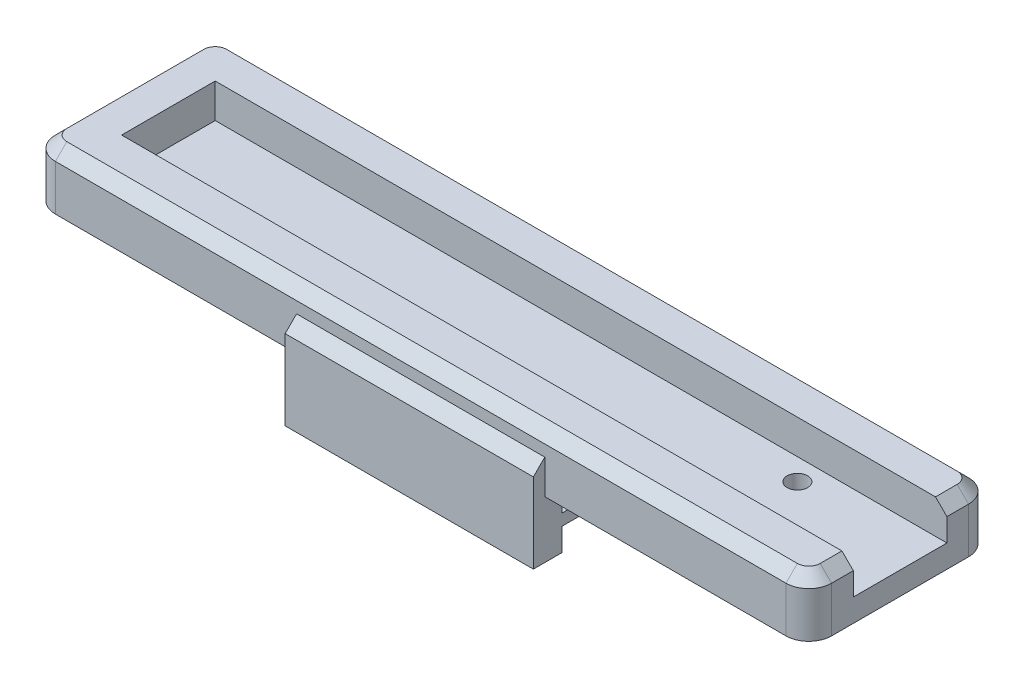
SolidWorks part; units mm, degrees
ref_plane "Front Plane" through (0, 0, 0) normal (0, 0, 1) x (1, 0, 0)
ref_plane "Top Plane" through (0, 0, 0) normal (0, 1, 0) x (1, 0, 0)
ref_plane "Right Plane" through (0, 0, 0) normal (1, 0, 0) x (0, 0, -1)
sketch "Sketch2" plane through (0, 0, 0) normal (0, 1, 0) x (1, 0, 0)
  line L1 (-34, 8) -> (34, 8)
  line L2 (-34, 8) -> (-34, -8)
  line L3 (-34, -8) -> (34, -8)
  line L4 (34, 8) -> (34, -8)
  line L5 (-34, 8) -> (34, -8) construction
  line L6 (-34, -8) -> (34, 8) construction
  line L7 (-30, 4) -> (30, 4) construction
  line L8 (-30, 4) -> (-30, -4) construction
  line L9 (-30, -4) -> (30, -4) construction
  line L10 (30, 4) -> (30, -4) construction
  line L11 (-30, 4) -> (30, -4) construction
  line L12 (-30, -4) -> (30, 4) construction
  point P0 (0, 0)
  point P5 (0, 0)
  dimension "D1" = 60
  dimension "D2" = 8
  dimension "D3" = 4
  dimension "D4" = 4
extrude "Boss-Extrude1" add sketch "Sketch2" along normal blind 2
sketch "Sketch3" plane through (0, 2, 0) normal (0, 1, 0) x (1, 0, 0)
  line L1 (-30.1, 4.1) -> (30.1, 4.1)
  line L2 (-30.1, 4.1) -> (-30.1, -4.1)
  line L3 (-30.1, -4.1) -> (30.1, -4.1)
  line L4 (30.1, 4.1) -> (30.1, -4.1)
  line L5 (-30.1, 4.1) -> (30.1, -4.1) construction
  line L6 (-30.1, -4.1) -> (30.1, 4.1) construction
  line L7 (-34, -8) -> (34, -8)
  line L8 (-34, -8) -> (-34, 8)
  line L9 (-34, 8) -> (34, 8)
  line L10 (34, -8) -> (34, 8)
  line L11 (-34, -8) -> (34, 8) construction
  line L12 (-34, 8) -> (34, -8) construction
  point P0 (0, 0)
  point P5 (0, 0)
  dimension "D1" = 8.2
  dimension "D2" = 60.2
extrude "Boss-Extrude2" add sketch "Sketch3" along normal blind 3
sketch "Sketch4" plane through (0, 2, 0) normal (0, 1, 0) x (1, 0, 0)
  line L0 (-30.1, 4.1) -> (-30.1, -4.1) construction
  line L1 (30.1, -4.1) -> (30.1, 4.1) construction
  line L2 (-30.1, -4.1) -> (30.1, -4.1) construction
  line L3 (30.1, 4.1) -> (-30.1, 4.1) construction
  circle A0 centre (-24.8, -2.2) radius 0.9
  circle A1 centre (22.8, 2.2) radius 0.9
  dimension "D1" = 1.8
  dimension "D2" = 1.8
  dimension "D3" = 5.3
  dimension "D4" = 7.3
  dimension "D5" = 1.9
  dimension "D6" = 1.9
extrude "Cut-Extrude1" cut sketch "Sketch4" against normal through all
sketch "Sketch5" plane through (0, 0, 0) normal (0, -1, 0) x (1, 0, 0)
  line L1 (-10.8716, 9) -> (10.8716, 9)
  line L2 (-10.8716, 9) -> (-10.8716, -9)
  line L3 (-10.8716, -9) -> (10.8716, -9)
  line L4 (10.8716, 9) -> (10.8716, -9)
  line L5 (-10.8716, 9) -> (10.8716, -9) construction
  line L6 (-10.8716, -9) -> (10.8716, 9) construction
  line L7 (-8.8716, 6.2692) -> (8.8716, 6.2692) construction
  line L8 (-8.8716, 6.2692) -> (-8.8716, -6.2692) construction
  line L9 (-8.8716, -6.2692) -> (8.8716, -6.2692) construction
  line L10 (8.8716, 6.2692) -> (8.8716, -6.2692) construction
  line L11 (-8.8716, 6.2692) -> (8.8716, -6.2692) construction
  line L12 (-8.8716, -6.2692) -> (8.8716, 6.2692) construction
  point P0 (0, 0)
  point P5 (0, 0)
  point P11 (10.8716, -9)
  dimension "D1" = 18
  dimension "D2" = 2
extrude "Boss-Extrude3" add sketch "Sketch5" along normal blind 5
sketch "Sketch6" plane through (-10.8716, 0, 0) normal (-1, 0, 0) x (0, 0, 1)
  line L0 (9, -5) -> (-9, -5) construction
  line L1 (-6.5, 0) -> (6.5, 0)
  line L2 (-6.5, 0) -> (-6.5, -5)
  line L3 (-6.5, -5) -> (6.5, -5)
  line L4 (6.5, 0) -> (6.5, -5)
  line L5 (-6.5, 0) -> (6.5, -5) construction
  line L6 (-6.5, -5) -> (6.5, 0) construction
  line L7 (-8, 0) -> (-9, 0) construction
  point P0 (0, -2.5)
  point P7 (-6.2526, 0.0211)
  point P8 (-6.2749, 0)
  point P11 (0, 0)
  dimension "D1" = 13
extrude "Cut-Extrude3" cut sketch "Sketch6" against normal up to surface (21.7431 mm away) up to face at (10.8716, -1.6667, 0)
sketch "Sketch7" plane through (-10.8716, 0, 0) normal (-1, 0, 0) x (0, 0, 1)
  line L5 (-6.5, 0) -> (-6.5, -5) construction
  line L6 (-6.5, -2) -> (-5, -2)
  line L7 (-6.5, -2) -> (-6.5, -3)
  line L8 (-6.5, -3) -> (-5, -3)
  line L9 (-5, -2) -> (-5, -3)
  line L10 (6.5, -5) -> (6.5, 0) construction
  line L11 (6.5, -2) -> (5, -2)
  line L12 (6.5, -2) -> (6.5, -3)
  line L13 (6.5, -3) -> (5, -3)
  line L14 (5, -2) -> (5, -3)
  line L15 (-9, -2.5) -> (9, -2.5) construction
  line L16 (-9, -5) -> (-9, 0) construction
  line L17 (9, -5) -> (9, 0) construction
  point P18 (5, -2.5)
  point P19 (-5, -2.5)
  dimension "D1" = 1.5
  dimension "D2" = 1.5
  dimension "D3" = 1
  dimension "D4" = 1
extrude "Boss-Extrude4" add sketch "Sketch7" against normal up to surface (21.7431 mm away) up to face at (10.8716, -2, 7.8)
chamfer "Chamfer1" distance 3 angle 45 2 edges at (0, 0, 8) (0, 0, -8)
sketch "Sketch8" plane through (0, 5, 0) normal (0, 1, 0) x (1, 0, 0)
  line L0 (34, -8) -> (34, 8) construction
  line L1 (30.1, -4.1) -> (34, -4.1)
  line L2 (30.1, -4.1) -> (30.1, 4.1)
  line L3 (30.1, 4.1) -> (34, 4.1)
  line L4 (34, -4.1) -> (34, 4.1)
  line L5 (30.1, 4.1) -> (-30.1, 4.1) construction
extrude "Cut-Extrude4" cut sketch "Sketch8" against normal up to surface (3 mm away) up to face at (-24.8, 2, 3.1)
fillet "Fillet1" radius 2 4 edges at (34, 2.5, 8) (34, 2.5, -8) (-34, 2.5, -8) (-34, 2.5, 8)
chamfer "Chamfer2" distance 1 angle 45 9 edges at (34, 5, 5.05) (33.4142, 5, 7.4142) (0, 5, 8) (-33.4142, 5, 7.4142) (34, 5, -5.05) (-34, 5, 0) (33.4142, 5, -7.4142) (-33.4142, 5, -7.4142) (0, 5, -8)
